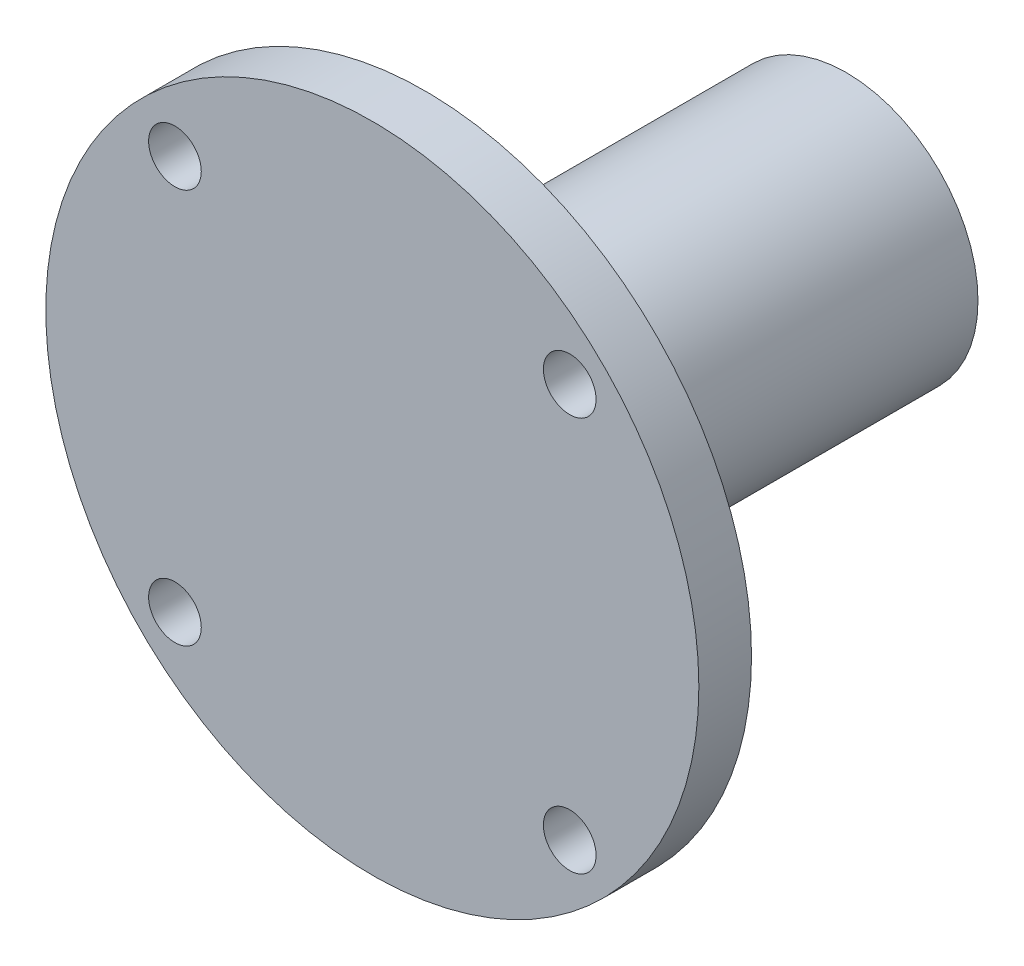
SolidWorks part; units mm, degrees
ref_plane "Płaszczyzna przednia" through (0, 0, 0) normal (0, 0, 1) x (1, 0, 0)
ref_plane "Płaszczyzna górna" through (0, 0, 0) normal (0, 1, 0) x (1, 0, 0)
ref_plane "Płaszczyzna prawa" through (0, 0, 0) normal (1, 0, 0) x (0, 0, -1)
sketch "Szkic1" plane through (0, 0, 0) normal (0, 0, 1) x (1, 0, 0)
  circle A0 centre (0, 0) radius 8
  circle A1 centre (0, 0) radius 12.5
  dimension "D1" = 16
extrude "Dodanie-wyciągnięcie1" add sketch "Szkic1" along normal blind 30
sketch "Szkic2" plane through (0, 0, 30) normal (0, 0, 1) x (1, 0, 0)
  circle A0 centre (0, 0) radius 20
  dimension "D1" = 40
extrude "Dodanie-wyciągnięcie3" add sketch "Szkic2" along normal blind 10
sketch "Szkic3" plane through (0, 0, 40) normal (0, 0, 1) x (1, 0, 0)
  circle A0 centre (0, 0) radius 31
  dimension "D1" = 62
extrude "Dodanie-wyciągnięcie4" add sketch "Szkic3" along normal blind 5
chamfer "Sfazowanie1" distance 10 angle 45 1 edges at (20, 0, 30)
sketch "Szkic4" plane through (0, 0, 45) normal (0, 0, 1) x (1, 0, 0)
  line L1 (-18.74, -18.74) -> (18.74, -18.74) construction
  line L2 (-18.74, -18.74) -> (-18.74, 18.74) construction
  line L3 (-18.74, 18.74) -> (18.74, 18.74) construction
  line L4 (18.74, -18.74) -> (18.74, 18.74) construction
  line L5 (-18.74, -18.74) -> (18.74, 18.74) construction
  line L6 (-18.74, 18.74) -> (18.74, -18.74) construction
  point P0 (0, 0)
  dimension "D1" = 37.48
  dimension "D2" = 37.48
hole_wizard "Otwory ustalające Ø5.0mm1" positions "Szkic 3D1" profile "Szkic5" hole size "Ø5.0" standard "DIN" end condition through all
sketch3d "Szkic 3D1"
  point P0 (-18.74, 18.74, 45)
  point P3 (18.74, 18.74, 45)
  point P6 (18.74, -18.74, 45)
  point P9 (-18.74, -18.74, 45)
sketch "Szkic5" plane through (-18.74, 18.74, 45) normal (1, 0, 0) x (0, -1, 0)
  line L0 (0, 0) -> (0, 45)
  line L1 (0, 45) -> (2.5, 45)
  line L2 (2.5, 45) -> (2.5, 0)
  line L5 (2.5, 0) -> (0, 0)
  line L11 (0, -6.35) -> (0, 107.95) construction
  dimension "Średnica otworu na wylot" = 5
  dimension "Głębokość otworu na wylot" = 45
